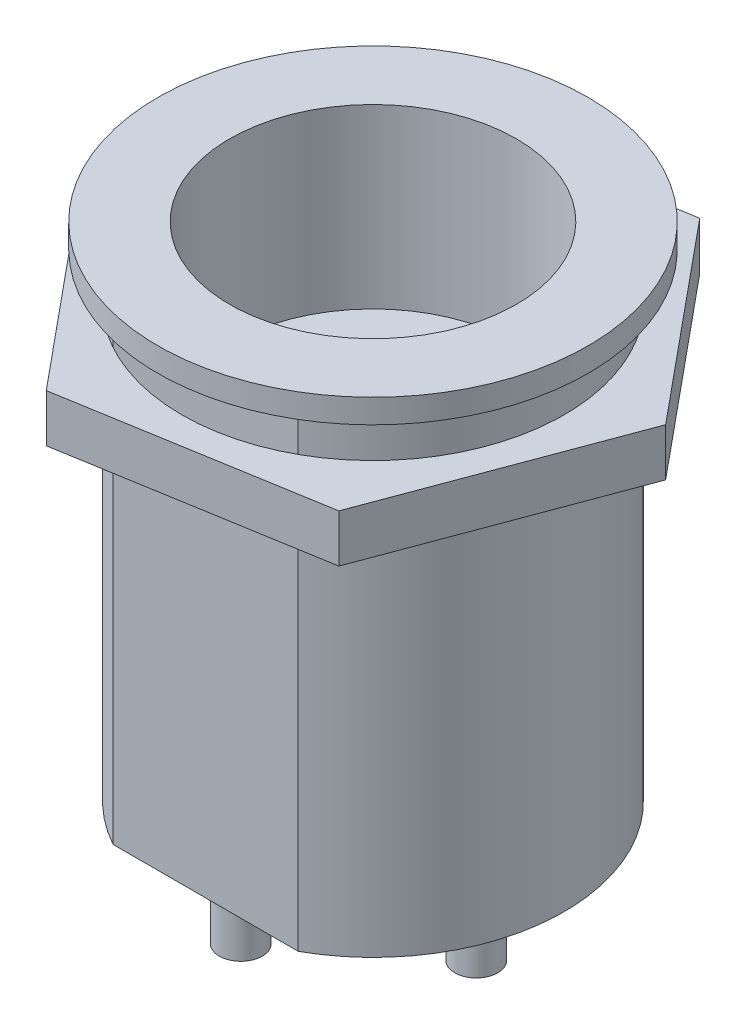
SolidWorks part; units mm, degrees
ref_plane "Front Plane" through (0, 0, 0) normal (0, 0, 1) x (1, 0, 0)
ref_plane "Top Plane" through (0, 0, 0) normal (0, 1, 0) x (1, 0, 0)
ref_plane "Right Plane" through (0, 0, 0) normal (1, 0, 0) x (0, 0, -1)
ref_axis "Axis1" through (0, 0, 0) along (0, 1, 0)
sketch "Sketch1" plane through (0, 0, 0) normal (0, 0, 1) x (1, 0, 0)
  line L0 (0, 0) -> (0, 38807.2134) construction
  line L1 (-9, 0) -> (-6, 0)
  line L2 (-6, 0) -> (-6, -7.4064)
  line L3 (-6, -7.4064) -> (0, -7.4064)
  line L4 (0, -7.4064) -> (0, -21)
  line L5 (0, -21) -> (-8, -21)
  line L6 (-8, -21) -> (-8, -1)
  line L7 (-8, -1) -> (-9, -1)
  line L8 (-9, -1) -> (-9, 0)
  dimension "D1" = 21
  dimension "D2" = 1
  dimension "D3" = 16
  dimension "D4" = 2
  dimension "D5" = 1
revolve "Revolve1" add sketch "Sketch1" angle 360 about L0
sketch "Sketch3" plane through (0, 0, 0) normal (0, 1, 0) x (1, 0, 0)
  line L1 (10.4778, 1.763) -> (3.7121, 9.9555)
  line L2 (3.7121, 9.9555) -> (-6.7657, 8.1925)
  line L3 (-6.7657, 8.1925) -> (-10.4778, -1.763)
  line L4 (-10.4778, -1.763) -> (-3.7121, -9.9555)
  line L5 (-3.7121, -9.9555) -> (6.7657, -8.1925)
  line L6 (6.7657, -8.1925) -> (10.4778, 1.763)
  circle A0 centre (0, 0) radius 8
  circle A1 centre (0, 0) radius 8 construction
  circle A2 centre (0, 0) radius 9.2016 construction
extrude "Boss-Extrude1" add sketch "Sketch3" against normal blind 2 from offset 3 separate body offset against normal yes
sketch "Sketch4" plane through (0, 0, 0) normal (0, 1, 0) x (1, 0, 0)
  circle A0 centre (0.6048, 4.9249) radius 0.9004
extrude "Boss-Extrude2" add sketch "Sketch4" against normal offset from surface (3 mm away) 23 from surface up to face at (0, -1, -8) offset beyond the face yes starting at face at (0, -21, -8)
pattern_circular "CirPattern1" count 4 over 360 about axis through (0, 0, 0) along (0, 1, 0) of "Boss-Extrude2"
sketch "Sketch5" plane through (0, 0, 0) normal (0, 1, 0) x (1, 0, 0)
  line L9 (-22.0254, -7) -> (22.0254, -7)
  line L10 (-22.0254, -7) -> (-22.0254, 7)
  line L11 (-22.0254, 7) -> (22.0254, 7)
  line L12 (22.0254, -7) -> (22.0254, 7)
  line L13 (-22.0254, -7) -> (22.0254, 7) construction
  line L14 (-22.0254, 7) -> (22.0254, -7) construction
  line L15 (-51.4369, -32.817) -> (51.4369, -32.817)
  line L16 (-51.4369, -32.817) -> (-51.4369, 32.817)
  line L17 (-51.4369, 32.817) -> (51.4369, 32.817)
  line L18 (51.4369, -32.817) -> (51.4369, 32.817)
  line L19 (-51.4369, -32.817) -> (51.4369, 32.817) construction
  line L20 (-51.4369, 32.817) -> (51.4369, -32.817) construction
  point P0 (0, 0)
  point P5 (0, 0)
  dimension "D1" = 14
extrude "Cut-Extrude1" cut sketch "Sketch5" against normal through all from surface starting at face at (0, -1, -8)
